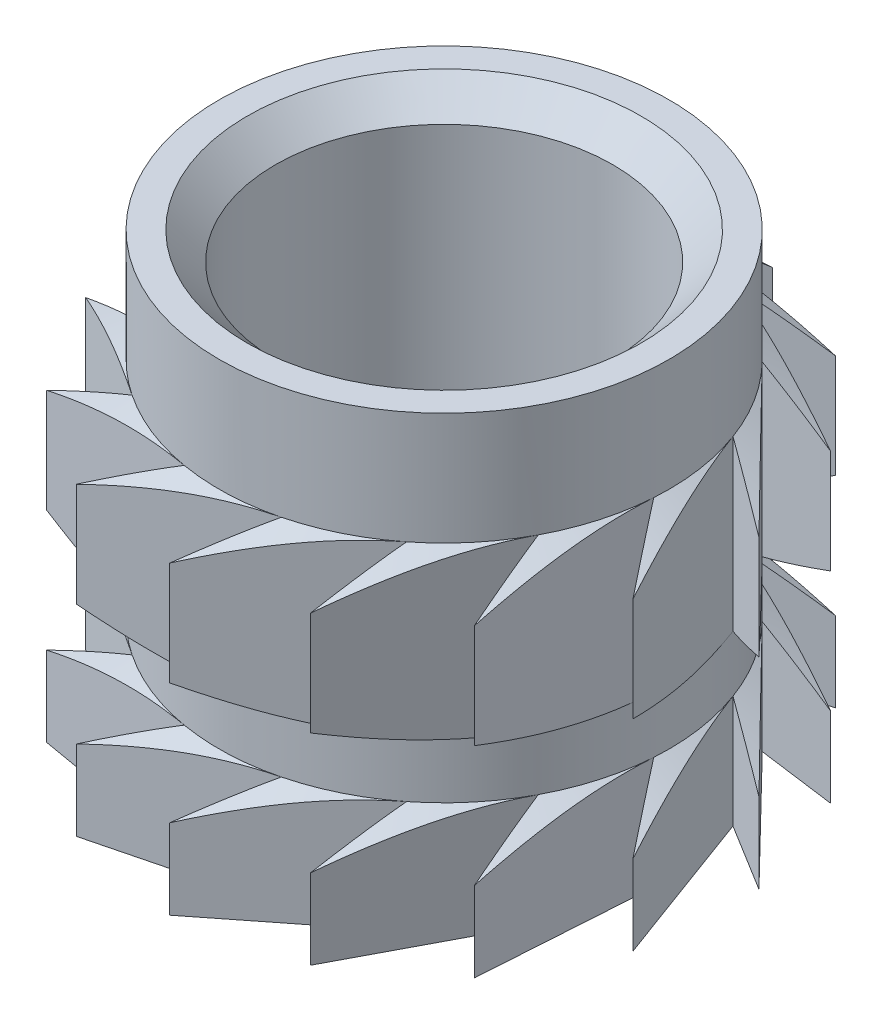
SolidWorks part; units mm, degrees
ref_plane "Front Plane" through (0, 0, 0) normal (0, 0, 1) x (1, 0, 0)
ref_plane "Top Plane" through (0, 0, 0) normal (0, 1, 0) x (1, 0, 0)
ref_plane "Right Plane" through (0, 0, 0) normal (1, 0, 0) x (0, 0, -1)
sketch "Sketch1" plane through (0, 0, 0) normal (0, 1, 0) x (1, 0, 0)
  circle A0 centre (0, 0) radius 1.5
  circle A1 centre (0, 0) radius 2
  dimension "D1" = 3
  dimension "D2" = 4
extrude "Boss-Extrude1" add sketch "Sketch1" along normal blind 4
sketch "Sketch2" plane through (0, 0, 0) normal (0, 0, 1) x (1, 0, 0)
  line L0 (-2, 0) -> (2, 0) construction
  line L1 (-2, 4) -> (-2, 0) construction
  line L2 (2, 4) -> (-2, 4) construction
  line L3 (2, 0) -> (2, 4) construction
  line L4 (-2, 0) -> (2, 0) construction
  line L5 (-2, 4) -> (-2, 0) construction
  line L6 (2, 4) -> (-2, 4) construction
  line L7 (2, 0) -> (2, 4) construction
  line L8 (2, 3) -> (2.5, 2.7113)
  line L9 (2.5, 2.7113) -> (2.5, 1.7887)
  line L10 (2.5, 1.7887) -> (2, 1.5)
  line L11 (2, 0) -> (2.5, 0)
  line L12 (2.5, 0) -> (2.5, 0.7113)
  line L13 (2.5, 0.7113) -> (2, 1)
  line L14 (2, 1) -> (2, 0)
  line L15 (2, 1.5) -> (2, 3)
  line L16 (0, 0) -> (0, 50000) construction
  dimension "D1" = 1
  dimension "D2" = 1.5
  dimension "D3" = 1
  dimension "D4" = 0.5
  dimension "D5" = 60
  dimension "D6" = 60
  dimension "D7" = 60
revolve "Revolve1" add sketch "Sketch2" angle 360 about L16
sketch "Sketch3" plane through (0, 4, 0) normal (0, 1, 0) x (1, 0, 0)
  line L0 (-0.0773, 1.9985) -> (1.4216, 2.0565)
  line L1 (1.4216, 2.0565) -> (0.7422, 1.8572)
  line L2 (0.7422, 1.8572) -> (2.1351, 1.3005)
  line L3 (2.1351, 1.3005) -> (1.4335, 1.3947)
  line L4 (1.4335, 1.3947) -> (2.4795, 0.3196)
  line L5 (2.4795, 0.3196) -> (1.8768, 0.6911)
  line L6 (1.8768, 0.6911) -> (2.3951, -0.7165)
  line L7 (2.3951, -0.7165) -> (1.9956, -0.132)
  line L8 (1.9956, -0.132) -> (1.8966, -1.6288)
  line L9 (1.8966, -1.6288) -> (1.7694, -0.9323)
  line L10 (1.7694, -0.9323) -> (1.0702, -2.2594)
  line L11 (1.0702, -2.2594) -> (1.2372, -1.5714)
  line L12 (1.2372, -1.5714) -> (0.0587, -2.4993)
  line L13 (0.0587, -2.4993) -> (0.4911, -1.9388)
  line L14 (0.4911, -1.9388) -> (-0.9629, -2.3071)
  line L15 (-0.9629, -2.3071) -> (-0.3399, -1.9709)
  line L16 (-0.3399, -1.9709) -> (-1.8181, -1.716)
  line L17 (-1.8181, -1.716) -> (-1.1122, -1.6623)
  line L18 (-1.1122, -1.6623) -> (-2.3589, -0.8281)
  line L19 (-2.3589, -0.8281) -> (-1.6921, -1.0662)
  line L20 (-1.6921, -1.0662) -> (-2.4918, 0.2029)
  line L21 (-2.4918, 0.2029) -> (-1.9795, -0.2858)
  line L22 (-1.9795, -0.2858) -> (-2.1938, 1.1988)
  line L23 (-2.1938, 1.1988) -> (-1.9246, 0.5441)
  line L24 (-1.9246, 0.5441) -> (-1.5165, 1.9875)
  line L25 (-1.5165, 1.9875) -> (-1.5369, 1.2798)
  line L26 (-1.5369, 1.2798) -> (-0.577, 2.4325)
  line L27 (-0.577, 2.4325) -> (-0.8835, 1.7943)
  line L28 (-0.8835, 1.7943) -> (0.4622, 2.4569)
  line L29 (0.4622, 2.4569) -> (-0.0773, 1.9985)
  circle A0 centre (0, 0) radius 2 construction
  circle A1 centre (0, 0) radius 2 construction
  circle A2 centre (0, 0) radius 2.5 construction
  arc A3 (-0.0773, 1.9985) -> (0.7422, 1.8572) centre (0, 0) cw
  arc A4 (0.7422, 1.8572) -> (1.4335, 1.3947) centre (0, 0) cw
  arc A5 (1.4335, 1.3947) -> (1.8768, 0.6911) centre (0, 0) cw
  arc A6 (1.8768, 0.6911) -> (1.9956, -0.132) centre (0, 0) cw
  arc A7 (1.9956, -0.132) -> (1.7694, -0.9323) centre (0, 0) cw
  arc A8 (1.7694, -0.9323) -> (1.2372, -1.5714) centre (0, 0) cw
  arc A9 (1.2372, -1.5714) -> (0.4911, -1.9388) centre (0, 0) cw
  arc A10 (0.4911, -1.9388) -> (-0.3399, -1.9709) centre (0, 0) cw
  arc A11 (-0.3399, -1.9709) -> (-1.1122, -1.6623) centre (0, 0) cw
  arc A12 (-1.1122, -1.6623) -> (-1.6921, -1.0662) centre (0, 0) cw
  arc A13 (-1.6921, -1.0662) -> (-1.9795, -0.2858) centre (0, 0) cw
  arc A14 (-1.9795, -0.2858) -> (-1.9246, 0.5441) centre (0, 0) cw
  arc A15 (-1.9246, 0.5441) -> (-1.5369, 1.2798) centre (0, 0) cw
  arc A16 (-1.5369, 1.2798) -> (-0.8835, 1.7943) centre (0, 0) cw
  arc A17 (-0.8835, 1.7943) -> (-0.0773, 1.9985) centre (0, 0) cw
  circle A18 centre (0, 0) radius 2.5
  circle A19 centre (0, 0) radius 2 construction
  point P53 (0, 0)
  dimension "D1" = 15
extrude "Cut-Extrude3" cut sketch "Sketch3" against normal through all contours L28 A18 L27 | L0 A18 L29 | L2 A18 L1 | L4 A18 L3 | L6 A18 L5 | L8 A18 L7 | L10 A18 L9 | L12 A18 L11 | L14 A18 L13 | L16 A18 L15 | L18 A18 L17 | L20 A18 L19 | L22 A18 L21 | L24 A18 L23 | L26 A18 L25 region at (0.6383, 4, -2.1816) region at (1.4705, 4, -1.7334) region at (-0.3043, 4, -2.2526) region at (2.0484, 4, -0.9855) region at (-1.1942, 4, -1.9341) region at (2.2721, 4, -0.0671) region at (-1.8776, 4, -1.2812) region at (-2.2364, 4, -0.4067) region at (2.103, 4, 0.8628) region at (-2.2085, 4, 0.5381) region at (1.5702, 4, 1.6436) region at (-1.7987, 4, 1.3898) region at (0.766, 4, 2.1402) region at (-1.0779, 4, 2.0013) region at (-0.1707, 4, 2.2667)
chamfer "Chamfer1" distance 0.25 angle 45 2 edges at (0, 4, 1.5) (0, 0, 1.5)
